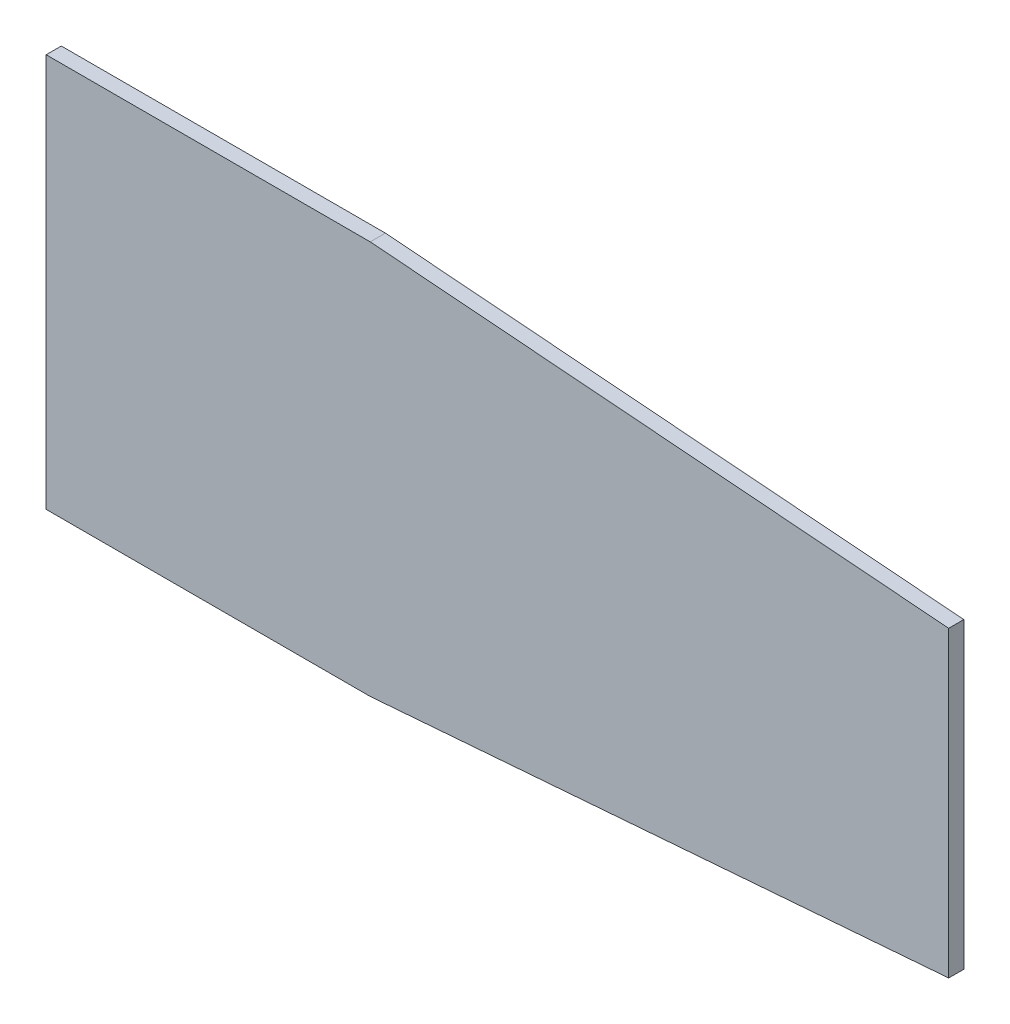
SolidWorks part; units mm, degrees
ref_plane "Ebene vorne" through (0, 0, 0) normal (0, 0, 1) x (1, 0, 0)
ref_plane "Ebene oben" through (0, 0, 0) normal (0, 1, 0) x (1, 0, 0)
ref_plane "Ebene rechts" through (0, 0, 0) normal (1, 0, 0) x (0, 0, -1)
sketch "Skizze1" plane through (0, 0, 0) normal (0, 0, 1) x (1, 0, 0)
  line L0 (0, 0) -> (298, 0) construction
  line L1 (0, -65) -> (0, 65)
  line L2 (0, 65) -> (107, 65)
  line L3 (107, 65) -> (298, 50)
  line L4 (298, 50) -> (298, -50)
  line L5 (107, -65) -> (298, -50)
  line L6 (0, -65) -> (107, -65)
  dimension "D1" = 130
  dimension "D2" = 298
  dimension "D3" = 100
  dimension "D4" = 191
extrude "Grundplatte" add sketch "Skizze1" along normal blind 5
